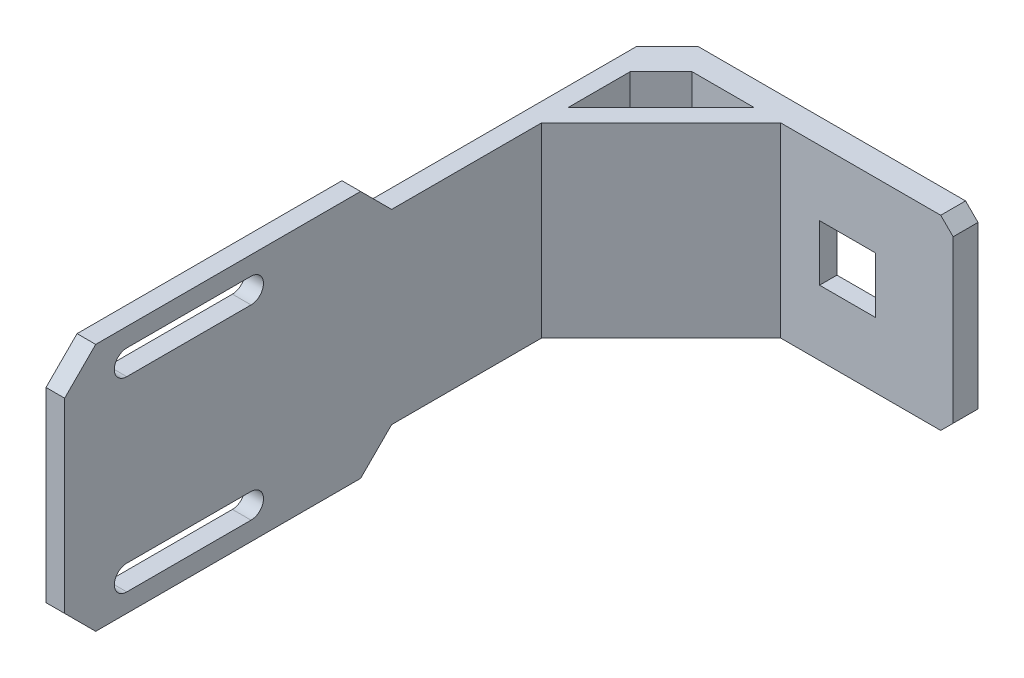
SolidWorks part; units mm, degrees
ref_plane "Alzado" through (0, 0, 0) normal (0, 0, 1) x (1, 0, 0)
ref_plane "Planta" through (0, 0, 0) normal (0, 1, 0) x (1, 0, 0)
ref_plane "Vista lateral" through (0, 0, 0) normal (1, 0, 0) x (0, 0, -1)
sketch "Croquis1" plane through (0, 0, 0) normal (0, 1, 0) x (1, 0, 0)
  line L0 (-0.35, 11.6655) -> (49.65, 11.6655)
  line L1 (-0.35, -88.3345) -> (2.65, -88.3345)
  line L2 (-0.35, -88.3345) -> (-0.35, 11.6655)
  line L4 (2.65, -88.3345) -> (2.65, -11.5772)
  line L5 (-0.35, -88.3345) -> (-0.1525, -38.501) construction
  line L6 (-0.35, 11.6655) -> (2.65, -88.3345) construction
  line L7 (49.65, 11.6655) -> (49.65, 7.6655)
  line L8 (49.65, 7.6655) -> (21.8927, 7.6655)
  line L9 (21.8927, 7.6655) -> (2.65, -11.5772)
  line L10 (17.65, 7.6655) -> (2.65, -7.3345)
  line L11 (17.65, 7.6655) -> (2.65, 7.6655)
  line L12 (2.65, -7.3345) -> (2.65, 7.6655)
  point P0 (0, 0)
  point P12 (0, 0)
  dimension "D1" = 4
  dimension "D2" = 50
  dimension "D3" = 3
  dimension "D4" = 45
  dimension "D5" = 3
  dimension "D6" = 15
  dimension "D7" = 100
extrude "Saliente-Extruir1" add sketch "Croquis1" along normal blind 40
sketch "Croquis2" plane through (-0.35, 0, 0) normal (-1, 0, 0) x (0, 0, 1)
  line L0 (58.3345, 35) -> (78.3345, 35) construction
  line L1 (58.3345, 37) -> (78.3345, 37)
  line L2 (58.3345, 33) -> (78.3345, 33)
  line L3 (58.3345, 5) -> (78.3345, 5) construction
  line L4 (58.3345, 7) -> (78.3345, 7)
  line L5 (58.3345, 3) -> (78.3345, 3)
  line L6 (68.3345, 35) -> (68.3345, 5) construction
  line L7 (-11.6655, 0) -> (88.3345, 0) construction
  line L8 (88.3345, 40) -> (88.3345, 0) construction
  arc A0 (58.3345, 37) -> (58.3345, 33) centre (58.3345, 35) ccw
  arc A1 (78.3345, 33) -> (78.3345, 37) centre (78.3345, 35) ccw
  arc A2 (58.3345, 7) -> (58.3345, 3) centre (58.3345, 5) ccw
  arc A3 (78.3345, 3) -> (78.3345, 7) centre (78.3345, 5) ccw
  point P2 (68.3345, 35)
  point P8 (68.3345, 5)
  point P14 (68.3345, 20)
  dimension "D5" = 2
  dimension "D6" = 2
  dimension "D1" = 30
  dimension "D2" = 20
  dimension "D3" = 10
  dimension "D4" = 20
extrude "Cortar-Extruir1" cut sketch "Croquis2" against normal through all
chamfer "Chaflán1" distance 5 angle 45 2 edges at (2.65, 20, -7.6655) (-0.35, 20, -11.6655)
sketch "Croquis3" plane through (-0.35, 0, 0) normal (-1, 0, 0) x (0, 0, 1)
  line L2 (-11.6655, 0) -> (40.7047, 0)
  line L3 (-11.6655, 0) -> (-11.6655, 5)
  line L5 (-11.6655, 5) -> (40.7047, 5)
  line L6 (40.7047, 0) -> (40.7047, 5)
  line L7 (-11.6655, 40) -> (40.7047, 40)
  line L8 (-11.6655, 40) -> (-11.6655, 35)
  line L9 (-11.6655, 35) -> (40.7047, 35)
  line L10 (40.7047, 40) -> (40.7047, 35)
  dimension "D1" = 30
extrude "Cortar-Extruir2" cut sketch "Croquis3" against normal through all
chamfer "Chaflán2" distance 5 angle 45 2 edges at (1.15, 35, 40.7047) (1.15, 5, 40.7047)
sketch "Croquis4" plane through (0, 0, -11.6655) normal (0, 0, -1) x (-1, 0, 0)
  line L0 (-49.65, 20) -> (0.35, 20) construction
  line L1 (-49.65, 35) -> (-49.65, 5) construction
  line L2 (0.35, 35) -> (0.35, 5) construction
  line L4 (-22.15, 7.5) -> (-47.15, 7.5)
  line L5 (-22.15, 7.5) -> (-22.15, 32.5)
  line L6 (-22.15, 32.5) -> (-47.15, 32.5)
  line L7 (-47.15, 7.5) -> (-47.15, 32.5)
  line L8 (-22.15, 7.5) -> (-47.15, 32.5) construction
  line L9 (-22.15, 32.5) -> (-47.15, 7.5) construction
  point P6 (-34.65, 20)
  dimension "D1" = 25
  dimension "D2" = 2.5
extrude "Cortar-Extruir3" cut sketch "Croquis4" against normal blind 1.2
sketch "Croquis5" plane through (0, 0, -10.4655) normal (0, 0, -1) x (-1, 0, 0)
  line L0 (-49.65, 20) -> (-4.65, 20) construction
  line L1 (-49.65, 35) -> (-49.65, 5) construction
  line L2 (-4.65, 5) -> (-4.65, 35) construction
  line L3 (-22.15, 7.5) -> (-22.15, 32.5) construction
  line L4 (-28.15, 15.5) -> (-37.15, 15.5)
  line L5 (-28.15, 15.5) -> (-28.15, 24.5)
  line L6 (-28.15, 24.5) -> (-37.15, 24.5)
  line L7 (-37.15, 15.5) -> (-37.15, 24.5)
  line L8 (-28.15, 15.5) -> (-37.15, 24.5) construction
  line L9 (-28.15, 24.5) -> (-37.15, 15.5) construction
  point P6 (-32.65, 20)
  dimension "D1" = 9
  dimension "D2" = 6
extrude "Cortar-Extruir4" cut sketch "Croquis5" against normal through all
sketch "Croquis6" plane through (0, 0, -10.4655) normal (0, 0, -1) x (-1, 0, 0)
  line L0 (-47.15, 32.5) -> (-47.15, 7.5) construction
  line L1 (-37.15, 24.5) -> (-47.15, 24.5)
  line L2 (-37.15, 24.5) -> (-37.15, 15.5)
  line L3 (-37.15, 15.5) -> (-47.15, 15.5)
  line L4 (-47.15, 24.5) -> (-47.15, 15.5)
  line L5 (-37.15, 15.5) -> (-28.15, 15.5) construction
extrude "Cortar-Extruir5" cut sketch "Croquis6" against normal blind 2
chamfer "Chaflán5" distance 2 angle 45 2 edges at (49.65, 5, -9.6655) (49.65, 35, -9.6655)
chamfer "Chaflán6" distance 5 angle 45 2 edges at (1.15, 0, 88.3345) (1.15, 40, 88.3345)
